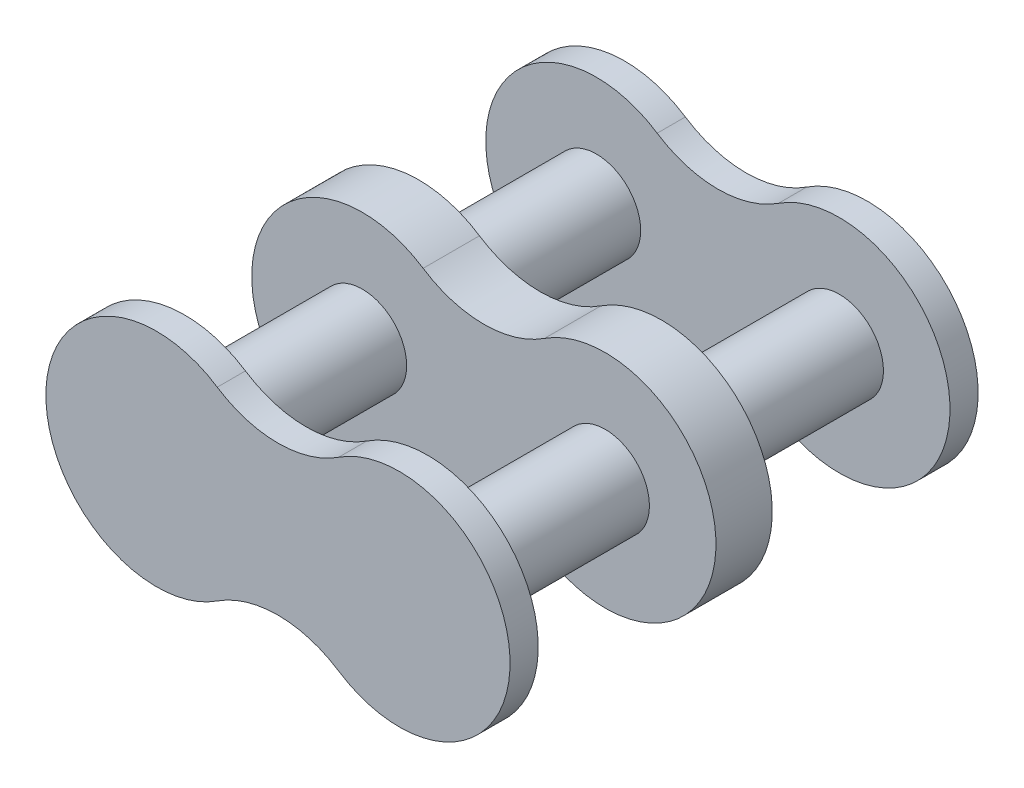
SolidWorks part; units mm, degrees
ref_plane "Front Plane" through (0, 0, 0) normal (0, 0, 1) x (1, 0, 0)
ref_plane "Top Plane" through (0, 0, 0) normal (0, 1, 0) x (1, 0, 0)
ref_plane "Right Plane" through (0, 0, 0) normal (1, 0, 0) x (0, 0, -1)
sketch "Sketch1" plane through (0, 0, 0) normal (0, 0, 1) x (1, 0, 0)
  line L0 (-3.175, 0) -> (3.175, 0) construction
  arc A0 (-1.5875, 2.4216) -> (-1.5875, -2.4216) centre (-3.175, 0) ccw
  arc A1 (1.5875, -2.4216) -> (1.5875, 2.4216) centre (3.175, 0) ccw
  arc A2 (-1.5875, 2.4216) -> (1.5875, 2.4216) centre (0, 4.8433) ccw
  arc A3 (-1.5875, -2.4216) -> (1.5875, -2.4216) centre (0, -4.8433) cw
  point P4 (0, 0)
  point P13 (-1.6413, -2.4631)
  point P14 (0, 0)
  point P15 (-1.6413, 2.4631)
  dimension "D2" = 5.7912
  dimension "D1" = 6.35
extrude "Boss-Extrude1" add sketch "Sketch1" along normal mid plane 1.4732
extrude "Boss-Extrude2" add sketch "Sketch1<2>" along normal blind 0.7366 from offset 5.3848 separate body
sketch "Sketch1<2>" plane through (0, 0, 0) normal (0, 0, 1) x (1, 0, 0) same geometry as "Sketch1"
sketch "Sketch2" plane through (0, 0, 0.7366) normal (0, 0, 1) x (1, 0, 0)
  circle A0 centre (-3.175, 0) radius 1.1557
  circle A1 centre (3.175, 0) radius 1.1557
  dimension "D1" = 2.3114
extrude "Boss-Extrude3" add sketch "Sketch2" along normal up to surface (4.6482 mm away) up to face at (0, 0, 5.3848)
extrude "Boss-Extrude4" add sketch "Sketch1<3>" against normal blind 0.7366 from offset 5.3848 separate body offset against normal yes
sketch "Sketch1<3>" plane through (0, 0, 0) normal (0, 0, 1) x (1, 0, 0) same geometry as "Sketch1"
extrude "Boss-Extrude5" add sketch "Sketch2<2>" against normal blind 4.6482 from surface starting at face at (0, 0, -0.7366)
sketch "Sketch2<2>" plane through (0, 0, 0.7366) normal (0, 0, 1) x (1, 0, 0) same geometry as "Sketch2"
